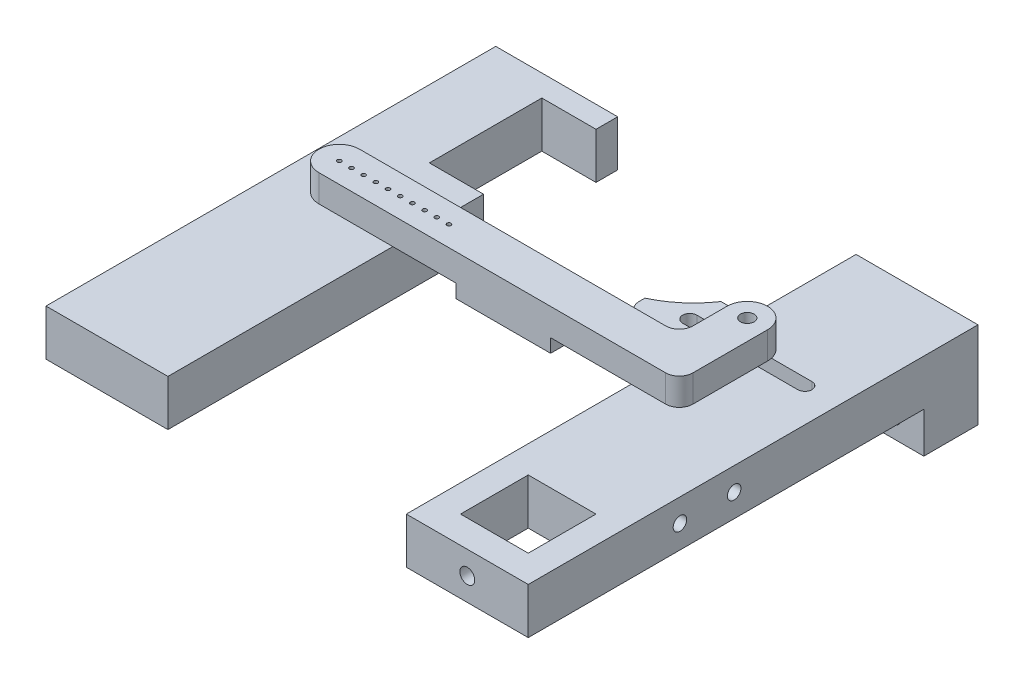
SolidWorks part; units mm, degrees
ref_plane "Front" through (0, 0, 0) normal (0, 0, 1) x (1, 0, 0)
ref_plane "Top" through (0, 0, 0) normal (0, 1, 0) x (1, 0, 0)
ref_plane "Right" through (0, 0, 0) normal (1, 0, 0) x (0, 0, -1)
sketch "Sketch1" plane through (0, 0, 0) normal (0, 1, 0) x (1, 0, 0)
  line L0 (0, 0) -> (0.465, -112) construction
  line L1 (88.995, 54) -> (38.065, 54)
  line L2 (88.995, 54) -> (88.995, -112)
  line L4 (38.065, 54) -> (38.065, 35)
  line L5 (3.065, 0) -> (-3.065, 0)
  line L9 (88.995, -112) -> (-88.065, -112)
  line L10 (-38.065, 35) -> (-38.065, 54)
  line L11 (-38.065, 54) -> (-88.065, 54)
  line L12 (-88.065, -112) -> (-88.065, 54)
  arc A0 (-3.065, 0) -> (-38.065, 35) centre (-3.065, 35) cw
  arc A1 (3.065, 0) -> (38.065, 35) centre (3.065, 35) ccw
  point P11 (0, 0)
  point P14 (-38.065, 0)
  point P18 (38.065, 0)
  dimension "D6" = 35
  dimension "D1" = 50.93
  dimension "D2" = 54
  dimension "D3" = 76.13
  dimension "D4" = 50
  dimension "D5" = 166
sketch "Sketch2" plane through (0, 0, 0) normal (0, 1, 0) x (1, 0, 0)
  line L0 (88.995, -112) -> (-88.065, -112) construction
  line L1 (88.995, 54) -> (43.995, 54)
  line L2 (88.995, 54) -> (88.995, -112)
  line L3 (88.995, -112) -> (43.995, -112)
  line L4 (43.995, 54) -> (43.995, -112)
  point P7 (88.995, 54)
  dimension "D1" = 45
extrude "Boss-Extrude1" add sketch "Sketch2" along normal blind 17
mirror "Mirror4" about plane through (0, 0, 0) normal (1, 0, 0) of bodies 103
sketch "Sketch6" plane through (0, 17, 0) normal (0, 1, 0) x (1, 0, 0)
  line L0 (43.995, 54) -> (43.995, -112) construction
  line L2 (43.995, 14) -> (43.995, -6)
  line L3 (43.995, -6) -> (18.995, -6)
  line L4 (88.995, 54) -> (38.065, 54) construction
  line L5 (43.995, 14) -> (34.1335, 14)
  line L6 (18.995, -6) -> (18.995, 1.0517)
  arc A1 (18.995, 1.0517) -> (34.1335, 14) centre (3.065, 35) ccw
  dimension "D3" = 75
  dimension "D1" = 40
  dimension "D2" = 20
  dimension "D4" = 25
extrude "Boss-Extrude3" add sketch "Sketch6" against normal up to surface (17 mm away) contours L2 L3 L6 A1 L5 up to face at (66.495, 0, 29)
sketch "Sketch3" plane through (0, 17, 0) normal (0, 1, 0) x (1, 0, 0)
  line L0 (33.995, 2.6) -> (76.495, 2.6) construction
  line L1 (33.995, 5.2) -> (76.495, 5.2)
  line L2 (33.995, 0) -> (76.495, 0)
  line L3 (3.065, 0) -> (-3.065, 0) construction
  line L6 (88.995, 54) -> (88.995, -112) construction
  line L8 (18.995, -6) -> (18.995, 1.0517) construction
  arc A1 (33.995, 5.2) -> (33.995, 0) centre (33.995, 2.6) ccw
  arc A2 (76.495, 0) -> (76.495, 5.2) centre (76.495, 2.6) ccw
  point P2 (55.245, 2.6)
  dimension "D1" = 2.6
  dimension "D2" = 15
  dimension "D3" = 12.5
extrude "Cut-Extrude1" cut sketch "Sketch3" against normal through all
sketch "Sketch4" plane through (0, 17, 0) normal (0, 1, 0) x (1, 0, 0)
  line L0 (57.745, -30) -> (-70.255, -30)
  line L1 (-70.255, -15) -> (42.745, -15)
  line L2 (3.065, 0) -> (-3.065, 0) construction
  line L3 (62.745, 2.6) -> (62.745, -25)
  line L4 (47.745, 2.6) -> (47.745, -10)
  line L7 (33.995, 2.6) -> (76.495, 2.6) construction
  circle A0 centre (55.245, 2.6) radius 2.5
  arc A1 (62.745, 2.6) -> (47.745, 2.6) centre (55.245, 2.6) ccw
  arc A2 (-70.255, -30) -> (-70.255, -15) centre (-70.255, -22.5) cw
  arc A10 (47.745, -10) -> (42.745, -15) centre (42.745, -10) cw
  arc A11 (62.745, -25) -> (57.745, -30) centre (57.745, -25) cw
  point P3 (38.5238, 2.6)
  point P18 (76.495, 2.6)
  point P20 (55.245, 2.6)
  dimension "D1" = 5
  dimension "D2" = 15
  dimension "D4" = 7.5
  dimension "D6" = 5
  dimension "D3" = 15
  dimension "D5" = 133
extrude "Boss-Extrude2" add sketch "Sketch4" along normal blind 10 from offset 1 separate body
sketch "Sketch5" plane through (0, 28, 0) normal (0, 1, 0) x (1, 0, 0)
  circle A0 centre (-70.255, -22.5) radius 0.75
  dimension "D1" = 1.5
extrude "Cut-Extrude2" cut sketch "Sketch5" against normal up to next (10 mm away)
pattern_linear "LPattern1" count 10 spacing 4.5 along (1, 0, 0) of "Cut-Extrude2"
sketch "Sketch7" plane through (0, 18, 0) normal (0, -1, 0) x (1, 0, 0)
  line L0 (-70.255, 30) -> (57.745, 30) construction
  line L1 (-19.755, 30) -> (15.245, 30)
  line L2 (-19.755, 30) -> (-19.755, 15)
  line L3 (-19.755, 15) -> (15.245, 15)
  line L4 (15.245, 30) -> (15.245, 15)
  line L5 (42.745, 15) -> (-70.255, 15) construction
  circle A0 centre (-29.755, 22.5) radius 0.75 construction
  dimension "D1" = 35
  dimension "D2" = 10
extrude "Boss-Extrude4" add sketch "Sketch7" along normal blind 5
fillet "Fillet1" radius 5 1 edges at (18.995, 8.5, 6)
sketch "Sketch8" plane through (0, 17, 0) normal (0, 1, 0) x (1, 0, 0)
  line L0 (-43.995, 54) -> (-43.995, -112) construction
  line L1 (-43.995, 46) -> (-63.995, 46)
  line L2 (-43.995, 46) -> (-43.995, 4.5)
  line L3 (-43.995, 4.5) -> (-63.995, 4.5)
  line L4 (-63.995, 46) -> (-63.995, 4.5)
  line L5 (-38.065, 54) -> (-88.065, 54) construction
  dimension "D1" = 20
  dimension "D2" = 41.5
  dimension "D3" = 8
extrude "Cut-Extrude3" cut sketch "Sketch8" against normal up to next (17 mm away)
sketch "Sketch9" plane through (0, 0, 0) normal (0, -1, 0) x (1, 0, 0)
  line L0 (88.995, -54) -> (88.995, 112) construction
  line L1 (43.995, -54) -> (88.995, -54)
  line L2 (43.995, -54) -> (43.995, -34)
  line L3 (43.995, -34) -> (88.995, -34)
  line L4 (88.995, -54) -> (88.995, -34)
  dimension "D1" = 20
extrude "Boss-Extrude5" add sketch "Sketch9" along normal blind 15
sketch "Sketch10" plane through (0, 0, -34) normal (0, 0, 1) x (1, 0, 0)
  line L0 (43.995, 0) -> (43.995, -15) construction
  line L1 (43.995, -7.5) -> (88.995, -7.5) construction
  line L2 (88.995, -15) -> (88.995, 0) construction
  circle A0 centre (53.4279, -7.5) radius 2.75
  circle A1 centre (77.8278, -7.5) radius 2.75
  point P12 (77.8278, -7.5)
  point P13 (53.4279, -7.5)
  dimension "D1" = 5.5
extrude "Cut-Extrude4" cut sketch "Sketch10" against normal up to next (20 mm away)
sketch "Sketch11" plane through (0, 17, 0) normal (0, 1, 0) x (1, 0, 0)
  line L0 (88.995, -112) -> (-88.065, -112) construction
  line L1 (53.995, -102) -> (78.995, -102)
  line L2 (53.995, -102) -> (53.995, -77)
  line L3 (53.995, -77) -> (78.995, -77)
  line L4 (78.995, -102) -> (78.995, -77)
  line L5 (88.995, 54) -> (88.995, -112) construction
  line L6 (43.995, -6) -> (43.995, -112) construction
  dimension "D1" = 10
  dimension "D2" = 10
  dimension "D3" = 10
  dimension "D4" = 25
extrude "Cut-Extrude5" cut sketch "Sketch11" against normal up to next (17 mm away)
sketch "Sketch12" plane through (0, 0, 112) normal (0, 0, 1) x (1, 0, 0)
  line L0 (43.995, 0) -> (88.995, 17) construction
  circle A0 centre (66.495, 8.5) radius 2.75
  dimension "D1" = 5.5
extrude "Cut-Extrude6" cut sketch "Sketch12" against normal up to next (10 mm away)
sketch "Sketch13" plane through (43.995, 0, 0) normal (-1, 0, 0) x (0, 0, 1)
  line L1 (112, 17) -> (112, 0) construction
  line L2 (6, 0) -> (6, 17) construction
  circle A0 centre (36, 8.5) radius 2.5
  circle A1 centre (56, 8.5) radius 2.5
  point P6 (112, 8.5)
  point P7 (59.4831, 8.0782)
  dimension "D3" = 5
  dimension "D1" = 20
  dimension "D2" = 30
extrude "Cut-Extrude7" cut sketch "Sketch13" against normal up to next (45 mm away)
